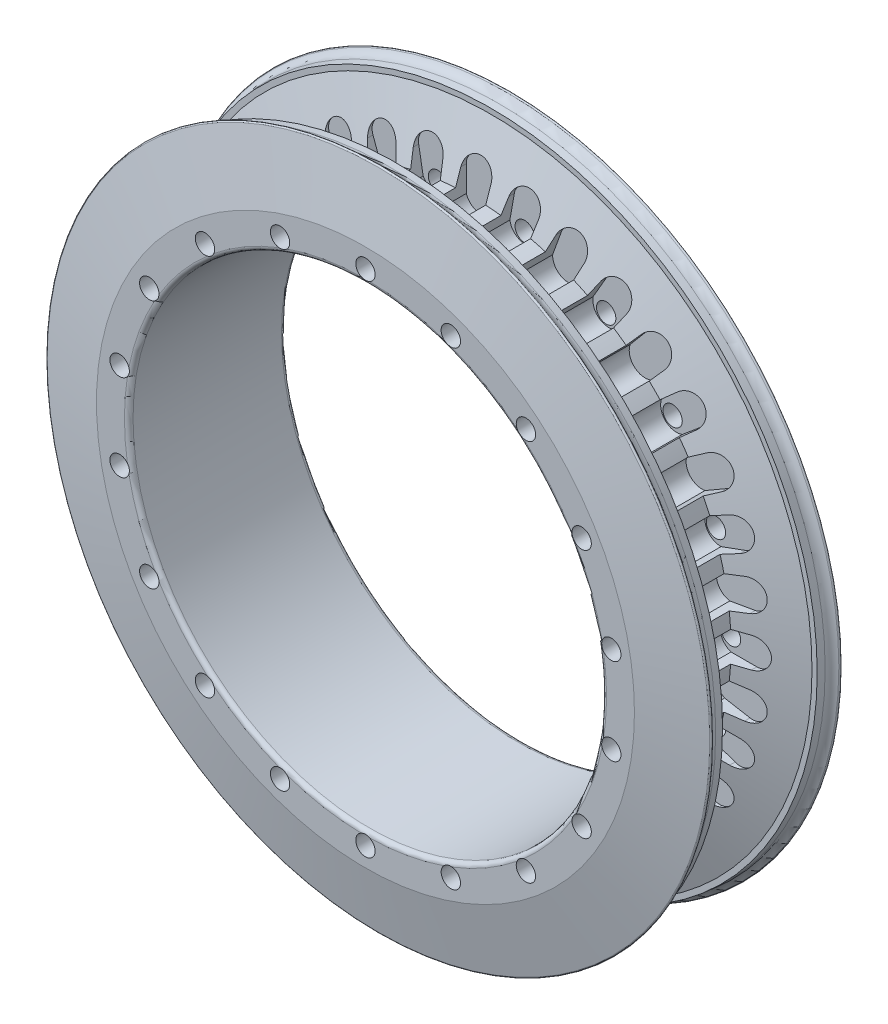
SolidWorks part; units mm, degrees
ref_plane "Alzado" through (0, 0, 0) normal (0, 0, 1) x (1, 0, 0)
ref_plane "Planta" through (0, 0, 0) normal (0, 1, 0) x (1, 0, 0)
ref_plane "Vista lateral" through (0, 0, 0) normal (1, 0, 0) x (0, 0, -1)
sketch "Croquis1" plane through (0, 0, 0) normal (1, 0, 0) x (0, 0, -1)
  line L0 (-496.2723, 0) -> (496.2723, 0) construction
  line L1 (0, 286.5) -> (0, -286.5) construction
  line L2 (-7.6059, 272.5) -> (7.6059, 272.5) construction
  line L3 (-8.0903, 272.876) -> (-8.1612, 273.1529) construction
  line L4 (-8.6072, 273.5275) -> (-12.7183, 273.8437) construction
  line L5 (-15.0067, 276.0215) -> (-16.1941, 285.374)
  line L6 (-16.1941, 285.374) -> (-14.21, 285.626) construction
  line L7 (-15.202, 285.5) -> (-14.4657, 279.7) construction
  line L8 (-14.4657, 279.7) -> (-15.0761, 284.508)
  line L9 (15.202, 285.5) -> (14.4657, 279.7) construction
  line L10 (16.1941, 285.374) -> (14.21, 285.626) construction
  line L11 (14.4657, 279.7) -> (15.0761, 284.508)
  line L12 (15.0067, 276.0215) -> (16.1941, 285.374)
  line L13 (8.6072, 273.5275) -> (12.7183, 273.8437) construction
  line L14 (8.0903, 272.876) -> (8.1612, 273.1529) construction
  line L15 (-11, 272.5) -> (11, 272.5) construction
  line L17 (-11, 272.5) -> (-6.1794, 258.5)
  line L18 (-6.1794, 258.5) -> (6.1794, 258.5)
  line L19 (6.1794, 258.5) -> (11, 272.5)
  line L20 (-11, 272.5) -> (-11, 273.7115)
  line L21 (11, 272.5) -> (11, 273.7115)
  line L22 (11, 273.7115) -> (12.7183, 273.8437)
  line L23 (-11, 273.7115) -> (-12.7183, 273.8437)
  arc A0 (-15.0761, 284.508) -> (-16.1941, 285.374) centre (-15.202, 285.5) ccw
  arc A1 (-14.4657, 279.7) -> (-9.4941, 275) centre (-14.9385, 274.2204) cw
  arc A2 (-9.4941, 275) -> (0, 274.3) centre (0.5356, 346.298) ccw
  arc A3 (-15.0067, 276.0215) -> (-12.7183, 273.8437) centre (-12.5266, 276.3364) ccw
  arc A4 (-7.6059, 272.5) -> (-8.0903, 272.876) centre (-7.6059, 273) cw construction
  arc A5 (-8.1612, 273.1529) -> (-8.6072, 273.5275) centre (-8.6456, 273.029) ccw construction
  arc A6 (9.4941, 275) -> (0, 274.3) centre (-0.5356, 346.298) cw
  arc A7 (8.1612, 273.1529) -> (8.6072, 273.5275) centre (8.6456, 273.029) cw construction
  arc A8 (7.6059, 272.5) -> (8.0903, 272.876) centre (7.6059, 273) ccw construction
  arc A9 (15.0067, 276.0215) -> (12.7183, 273.8437) centre (12.5266, 276.3364) cw
  arc A10 (14.4657, 279.7) -> (9.4941, 275) centre (14.9385, 274.2204) ccw
  arc A11 (15.0761, 284.508) -> (16.1941, 285.374) centre (15.202, 285.5) cw
  point P0 (-15.202, 286.5)
  point P3 (0, 0)
  point P6 (0, 0)
  point P9 (0, 272.5)
  point P25 (-14.75, 274)
  point P28 (-7.9941, 272.5)
  point P31 (-8.25, 273.5)
  point P49 (8.25, 273.5)
  point P50 (7.9941, 272.5)
  point P51 (14.75, 274)
  point P52 (15.202, 286.5)
  point P55 (0, 272.5)
  dimension "D2" = 15.6
  dimension "D7" = 14
  dimension "D8" = 29.5
  dimension "D9" = 6.8
  dimension "D10" = 11.5
  dimension "D11" = 5.5
  dimension "D6" = 2
  dimension "D14" = 72
  dimension "D16" = 2.5
  dimension "D17" = 0.5
  dimension "D1" = 272.5
  dimension "D3" = 1
  dimension "D4" = 548
  dimension "D5" = 8.2
  dimension "D12" = 6.7
  dimension "D13" = 0.7
  dimension "D15" = 6.5
  dimension "D18" = 22
  dimension "D19" = 38
  dimension "D20" = 14
sketch "Croquis2" plane through (0, 0, 0) normal (1, 0, 0) x (0, 0, -1)
  line L0 (-17.25, 253) -> (17.25, 253)
  line L1 (0, 286.5) -> (0, -286.5) construction
  line L2 (-18.25, 254) -> (-18.25, 260.5)
  line L3 (-20.25, 262.5) -> (-23.25, 262.5) construction
  line L4 (-23.25, 262.5) -> (-23.25, 253) construction
  line L5 (-23.25, 198) -> (23.25, 198) construction
  line L6 (23.25, 262.5) -> (23.25, 253) construction
  line L7 (-496.2723, 0) -> (496.2723, 0) construction
  line L8 (0, 286.5) -> (0, -286.5) construction
  line L9 (-18.25, 260.5) -> (-15.227, 274.9669)
  line L10 (11, 273.7115) -> (12.7183, 273.8437) construction
  line L11 (11, 272.5) -> (11, 273.7115) construction
  line L12 (6.1794, 258.5) -> (11, 272.5) construction
  line L13 (-6.1794, 258.5) -> (6.1794, 258.5) construction
  line L14 (-11, 272.5) -> (-6.1794, 258.5) construction
  line L15 (-11, 272.5) -> (-11, 273.7115) construction
  line L16 (-11, 273.7115) -> (-12.7183, 273.8437) construction
  line L17 (11, 273.7115) -> (12.7183, 273.8437)
  line L18 (11, 272.5) -> (11, 273.7115)
  line L19 (6.1794, 258.5) -> (11, 272.5)
  line L20 (-6.1794, 258.5) -> (6.1794, 258.5)
  line L21 (-11, 272.5) -> (-6.1794, 258.5)
  line L22 (-11, 272.5) -> (-11, 273.7115)
  line L23 (-11, 273.7115) -> (-12.7183, 273.8437)
  line L24 (20.25, 262.5) -> (23.25, 262.5) construction
  line L25 (18.25, 254) -> (18.25, 260.5)
  line L26 (18.25, 260.5) -> (15.227, 274.9669)
  arc A0 (-17.25, 253) -> (-18.25, 254) centre (-17.25, 254) cw
  arc A1 (-18.25, 260.5) -> (-20.25, 262.5) centre (-20.25, 260.5) ccw construction
  arc A2 (12.7183, 273.8437) -> (15.0067, 276.0215) centre (12.5266, 276.3364) ccw construction
  arc A3 (-15.0067, 276.0215) -> (-12.7183, 273.8437) centre (-12.5266, 276.3364) ccw construction
  arc A4 (12.7183, 273.8437) -> (14.6755, 275.0588) centre (12.5266, 276.3364) ccw
  arc A5 (-14.6755, 275.0588) -> (-12.7183, 273.8437) centre (-12.5266, 276.3364) ccw
  arc A6 (-14.6755, 275.0588) -> (-15.227, 274.9669) centre (-14.9334, 274.9055) ccw
  arc A7 (14.6755, 275.0588) -> (15.227, 274.9669) centre (14.9334, 274.9055) cw
  arc A8 (18.25, 260.5) -> (20.25, 262.5) centre (20.25, 260.5) cw construction
  arc A9 (17.25, 253) -> (18.25, 254) centre (17.25, 254) ccw
  point P3 (0, 253)
  point P9 (0, 198)
  point P18 (-18.25, 253)
  point P21 (-18.25, 262.5)
  dimension "D6" = 1
  dimension "D7" = 2
  dimension "D8" = 0.3
  dimension "D1" = 35.5
  dimension "D2" = 9.5
  dimension "D3" = 5
  dimension "D4" = 110
  dimension "D5" = 198
revolve "Revolución2" add sketch "Croquis2" angle 360 about L5
sketch "Croquis3" plane through (0, 0, 0) normal (0, 0, 1) x (1, 0, 0)
  circle A0 centre (0, 256) radius 2.25
  circle A1 centre (0, 198) radius 58 construction
  circle A2 centre (19.8372, 252.5022) radius 2.25
  circle A3 centre (37.2817, 242.4306) radius 2.25
  circle A4 centre (50.2295, 227) radius 2.25
  circle A5 centre (57.1188, 208.0716) radius 2.25
  circle A6 centre (57.1188, 187.9284) radius 2.25
  circle A7 centre (50.2295, 169) radius 2.25
  circle A8 centre (37.2817, 153.5694) radius 2.25
  circle A9 centre (19.8372, 143.4978) radius 2.25
  circle A10 centre (0, 140) radius 2.25
  circle A11 centre (-19.8372, 143.4978) radius 2.25
  circle A12 centre (-37.2817, 153.5694) radius 2.25
  circle A13 centre (-50.2295, 169) radius 2.25
  circle A14 centre (-57.1188, 187.9284) radius 2.25
  circle A15 centre (-57.1188, 208.0716) radius 2.25
  circle A16 centre (-50.2295, 227) radius 2.25
  circle A17 centre (-37.2817, 242.4306) radius 2.25
  circle A18 centre (-19.8372, 252.5022) radius 2.25
  arc A19 (0, 256) -> (19.8372, 252.5022) centre (0, 198) cw
  point P6 (10.0716, 255.1188)
  point P41 (0, 198)
  dimension "D1" = 4.5
  dimension "D2" = 58
  dimension "D3" = 18
extrude "Cortar-Extruir1" cut sketch "Croquis3" along normal through all from offset 6.18 contours A12 | A11 | A13 | A10 | A9 | A8 | A7 | A6 | A5 | A4 | A3 | A2 | A0 | A14 | A15 | A16 | A17 | A18 offset against normal yes
sketch "Croquis4" plane through (0, 0, 0) normal (0, 0, 1) x (1, 0, 0)
  circle A0 centre (10.0716, 255.1188) radius 2.25
  circle A1 centre (0, 198) radius 58 construction
  circle A2 centre (0, 198) radius 58 construction
  circle A3 centre (29, 248.2295) radius 2.25
  circle A4 centre (44.4306, 235.2817) radius 2.25
  circle A5 centre (54.5022, 217.8372) radius 2.25
  circle A6 centre (58, 198) radius 2.25
  circle A7 centre (54.5022, 178.1628) radius 2.25
  circle A8 centre (44.4306, 160.7183) radius 2.25
  circle A9 centre (29, 147.7705) radius 2.25
  circle A10 centre (10.0716, 140.8812) radius 2.25
  circle A11 centre (-10.0716, 140.8812) radius 2.25
  circle A12 centre (-29, 147.7705) radius 2.25
  circle A13 centre (-44.4306, 160.7183) radius 2.25
  circle A14 centre (-54.5022, 178.1628) radius 2.25
  circle A15 centre (-58, 198) radius 2.25
  circle A16 centre (-54.5022, 217.8372) radius 2.25
  circle A17 centre (-44.4306, 235.2817) radius 2.25
  circle A18 centre (-29, 248.2295) radius 2.25
  circle A19 centre (-10.0716, 255.1188) radius 2.25
  point P42 (0, 198)
  dimension "D1" = 4.5
  dimension "D2" = 18
extrude "Cortar-Extruir2" cut sketch "Croquis4" against normal through all from offset 6.18
sketch "Croquis5" plane through (0, 0, 0) normal (0, 0, 1) x (1, 0, 0)
  line L0 (0, 256) -> (0, 262) construction
  line L5 (-3.5, 256) -> (-3.5, 262)
  line L6 (3.5, 256) -> (3.5, 262)
  arc A1 (-3.5, 256) -> (3.5, 256) centre (0, 257.2) ccw
  arc A6 (3.5, 262) -> (-3.5, 262) centre (0, 262) ccw
  circle A7 centre (0, 198) radius 58 construction
  circle A8 centre (0, 256) radius 2.25 construction
  circle A9 centre (0, 256) radius 2.25 construction
  point P7 (0, 259)
  point P12 (0, 253.5)
  dimension "D2" = 6
  dimension "D3" = 3.5
  dimension "D5" = 116
  dimension "D1" = 7
  dimension "D4" = 2.5
extrude "Cortar-Extruir4" cut sketch "Croquis5" against normal blind 8.68 and the other way blind 8.68 contours L6 A6 L5 A1 region at (0, 259.469, 0)
pattern_circular "MatrizC1" count 36 over 360 about axis through (0, 198, 18.25) along (0, 0, 1) of "Cortar-Extruir4"
